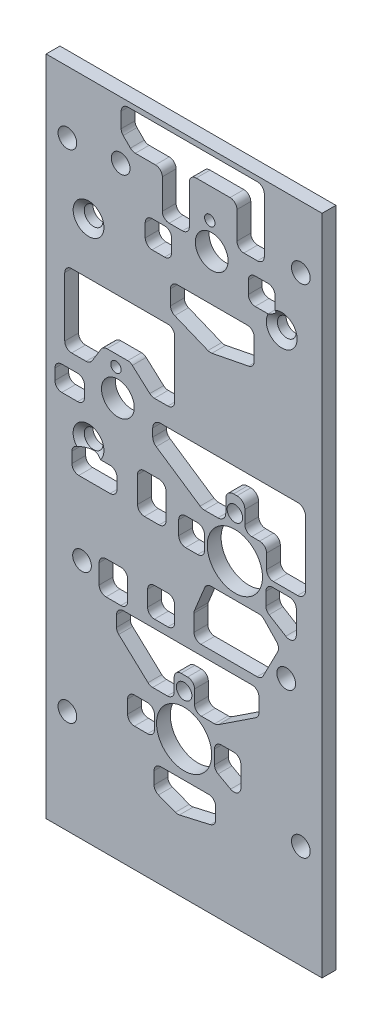
SolidWorks part; units mm, degrees
material "Acrylic (Medium-high impact)"
ref_plane "Front Plane" through (0, 0, 0) normal (0, 0, 1) x (1, 0, 0)
ref_plane "Top Plane" through (0, 0, 0) normal (0, 1, 0) x (1, 0, 0)
ref_plane "Right Plane" through (0, 0, 0) normal (1, 0, 0) x (0, 0, -1)
sketch "Sketch1" plane through (0, 0, 0) normal (0, 0, 1) x (1, 0, 0)
  line L8 (31.75, -152.4) -> (31.75, 0)
  line L9 (31.75, 0) -> (-31.75, 0)
  line L10 (-31.75, 0) -> (-31.75, -152.4)
  line L11 (-31.75, -152.4) -> (31.75, -152.4)
extrude "Boss-Extrude1" add sketch "Sketch1" against normal blind 3.175
hole_wizard "#6 Clearance Hole1" positions "Sketch3" profile "Sketch2" hole size "#6" standard "ANSI Inch" end condition up to next
sketch "Sketch3" plane through (0, 0, 0) normal (0, 0, 1) x (1, 0, 0)
  point P0 (-26.8605, -14.2875)
  point P2 (26.8605, -14.2875)
  point P4 (26.8605, -128.5875)
  point P6 (-26.8605, -128.5875)
sketch "Sketch2" plane through (-26.8605, -14.2875, 0) normal (1, 0, 0) x (0, -1, 0)
  line L0 (0, 0) -> (0, 3.175)
  line L1 (0, 3.175) -> (2.1526, 3.175)
  line L2 (2.1526, 3.175) -> (2.1526, 0)
  line L5 (2.1526, 0) -> (0, 0)
  line L11 (0, -6.35) -> (0, 107.95) construction
  dimension "Thru Hole Dia." = 4.3053
  dimension "Thru Hole Depth" = 3.175
hole_wizard "#6 Clearance Hole2" positions "Sketch5" profile "Sketch4" hole size "#6" standard "ANSI Inch" end condition up to next
sketch "Sketch5" plane through (0, 0, 0) normal (0, 0, 1) x (1, 0, 0)
  point P0 (-23.495, -96.8375)
  point P2 (23.495, -96.8375)
  point P4 (-14.605, -13.208)
sketch "Sketch4" plane through (-23.495, -96.8375, 0) normal (1, 0, 0) x (0, -1, 0)
  line L0 (0, 0) -> (0, 3.175)
  line L1 (0, 3.175) -> (2.1526, 3.175)
  line L2 (2.1526, 3.175) -> (2.1526, 0)
  line L5 (2.1526, 0) -> (0, 0)
  line L11 (0, -6.35) -> (0, 107.95) construction
  dimension "Thru Hole Dia." = 4.3053
  dimension "Thru Hole Depth" = 3.175
hole_wizard "1/2 (0.5) Diameter Hole1" positions "Sketch7" profile "Sketch6" hole size "1/2" standard "ANSI Inch" end condition up to next
sketch "Sketch7" plane through (0, 0, 0) normal (0, 0, 1) x (1, 0, 0)
  point P4 (11.684, -79.375)
  point P6 (0, -120.65)
sketch "Sketch6" plane through (11.684, -79.375, 0) normal (1, 0, 0) x (0, -1, 0)
  line L0 (0, 0) -> (0, 3.175)
  line L1 (0, 3.175) -> (6.35, 3.175)
  line L2 (6.35, 3.175) -> (6.35, 0)
  line L5 (6.35, 0) -> (0, 0)
  line L11 (0, -6.35) -> (0, 107.95) construction
  dimension "Thru Hole Dia." = 12.7
  dimension "Thru Hole Depth" = 3.175
hole_wizard "9/64 (0.14063) Diameter Hole1" positions "Sketch9" profile "Sketch8" hole size "9/64" standard "ANSI Inch" end condition up to next
sketch "Sketch9" plane through (0, 0, 0) normal (0, 0, 1) x (1, 0, 0)
  point P0 (0, -111.125)
  point P2 (11.684, -69.85)
sketch "Sketch8" plane through (0, -111.125, 0) normal (1, 0, 0) x (0, -1, 0)
  line L0 (0, 0) -> (0, 3.175)
  line L1 (0, 3.175) -> (1.786, 3.175)
  line L2 (1.786, 3.175) -> (1.786, 0)
  line L5 (1.786, 0) -> (0, 0)
  line L11 (0, -6.35) -> (0, 107.95) construction
  dimension "Thru Hole Dia." = 3.572
  dimension "Thru Hole Depth" = 3.175
hole_wizard "19/64 (0.29688) Diameter Hole1" positions "Sketch11" profile "Sketch10" hole size "19/64" standard "ANSI Inch" end condition up to next
sketch "Sketch11" plane through (0, 0, 0) normal (0, 0, 1) x (1, 0, 0)
  point P0 (-15.24, -60.325)
  point P2 (6.35, -20.32)
sketch "Sketch10" plane through (-15.24, -60.325, 0) normal (1, 0, 0) x (0, -1, 0)
  line L0 (0, 0) -> (0, 3.175)
  line L1 (0, 3.175) -> (3.7704, 3.175)
  line L2 (3.7704, 3.175) -> (3.7704, 0)
  line L5 (3.7704, 0) -> (0, 0)
  line L11 (0, -6.35) -> (0, 107.95) construction
  dimension "Thru Hole Dia." = 7.5408
  dimension "Thru Hole Depth" = 3.175
hole_wizard "CSK for #6 Flat Head Machine Screw (100)1" positions "Sketch12" profile "Sketch13" countersink size "#6" standard "ANSI Inch" end condition up to next
sketch "Sketch12" plane through (0, 0, 0) normal (0, 0, 1) x (1, 0, 0)
  circle A0 centre (-21.99, -72.39) radius 2.15 construction
  circle A1 centre (-21.99, -27.94) radius 2.15 construction
  circle A2 centre (22.46, -27.94) radius 2.15 construction
  point P0 (-21.99, -72.39)
  point P5 (-21.99, -27.94)
  point P7 (22.46, -27.94)
sketch "Sketch13" plane through (-21.99, -72.39, 0) normal (1, 0, 0) x (0, -1, 0)
  line L0 (0, 0) -> (0, 3.175)
  line L1 (0, 3.175) -> (2.1526, 3.175)
  line L2 (2.1526, 3.175) -> (2.1526, 1.1669)
  line L3 (2.1526, 1.1669) -> (3.5433, 0)
  line L5 (3.5433, 0) -> (0, 0)
  line L6 (-2.1526, 1.1669) -> (-3.5433, 0) construction
  line L11 (0, -6.35) -> (0, 107.95) construction
  dimension "Thru Hole Dia." = 4.3053
  dimension "Thru Hole Depth" = 3.175
  dimension "Near C'Sink Dia." = 7.0866
  dimension "Near C'Sink Angle" = 100
hole_wizard "3/32 (0.09375) Diameter Hole1" positions "Sketch14" profile "Sketch15" hole size "3/32" standard "ANSI Inch" end condition up to next
sketch "Sketch14" plane through (0, 0, 0) normal (0, 0, 1) x (1, 0, 0)
  line L0 (-11.9489, -54.0615) -> (-19.4279, -54.622) construction
  line L1 (9.6411, -14.0565) -> (2.1621, -14.617) construction
  point P0 (-15.6884, -54.3418)
  point P4 (5.9016, -14.3368)
sketch "Sketch15" plane through (-15.6884, -54.3418, 0) normal (1, 0, 0) x (0, -1, 0)
  line L0 (0, 0) -> (0, 3.175)
  line L1 (0, 3.175) -> (1.1906, 3.175)
  line L2 (1.1906, 3.175) -> (1.1906, 0)
  line L5 (1.1906, 0) -> (0, 0)
  line L11 (0, -6.35) -> (0, 107.95) construction
  dimension "Thru Hole Dia." = 2.3812
  dimension "Thru Hole Depth" = 3.175
sketch "Sketch16" plane through (0, 0, 0) normal (0, 0, 1) x (1, 0, 0)
  line L0 (-8.9463, -22.2122) -> (-8.9463, -25.2501)
  line L1 (-12.8969, -1.1704) -> (16.8634, -1.1704)
  line L2 (18.4509, -2.7579) -> (18.4509, -15.3315)
  line L3 (16.8634, -16.919) -> (13.7539, -16.919)
  line L4 (12.1664, -15.3315) -> (12.1664, -9.0413)
  line L5 (10.5789, -7.4538) -> (2.798, -7.4538)
  line L6 (1.2105, -9.0413) -> (1.2105, -17.9777)
  line L7 (-0.377, -19.5652) -> (-3.4256, -19.5652)
  line L8 (-5.0131, -17.9777) -> (-5.0131, -11.1146)
  line L9 (-6.6006, -9.5271) -> (-11.2247, -9.5271)
  line L10 (-12.3472, -9.0621) -> (-14.0195, -7.3899)
  line L11 (-14.4844, -6.2674) -> (-14.4844, -2.7579)
  line L12 (-7.3588, -20.6247) -> (-4.4726, -20.6247)
  line L13 (-2.8851, -22.2122) -> (-2.8851, -25.2501)
  line L14 (-4.4726, -26.8376) -> (-7.3588, -26.8376)
  line L15 (14.7691, -21.7812) -> (14.7691, -24.6709)
  line L16 (16.3566, -26.2584) -> (19.3318, -26.2584)
  line L17 (20.9193, -24.6709) -> (20.9193, -21.7812)
  line L18 (19.3318, -20.1937) -> (16.3566, -20.1937)
  line L19 (-1.5492, -30.8932) -> (14.5429, -30.8932)
  line L20 (16.1304, -32.4807) -> (16.1304, -37.3513)
  line L21 (14.8494, -38.909) -> (6.3904, -40.5735)
  line L22 (5.4811, -40.4844) -> (-2.152, -37.3513)
  line L23 (-3.1367, -35.8827) -> (-3.1367, -32.4807)
  line L24 (-25.8787, -39.8413) -> (-3.7395, -39.8413)
  line L25 (-2.152, -41.4288) -> (-2.152, -54.5712)
  line L26 (-3.7395, -56.1587) -> (-6.8312, -56.1587)
  line L27 (-7.8927, -55.7517) -> (-11.9102, -52.1393)
  line L28 (-12.9716, -51.7323) -> (-17.7428, -51.7323)
  line L29 (-19.0941, -52.4865) -> (-21.1969, -55.8964)
  line L30 (-22.5481, -56.6506) -> (-25.8787, -56.6506)
  line L31 (-27.4662, -55.0631) -> (-27.4662, -41.4288)
  line L32 (-28.1475, -60.0018) -> (-24.5023, -60.0018)
  line L33 (-22.9148, -61.5893) -> (-22.9148, -64.0639)
  line L34 (-24.5023, -65.6514) -> (-28.1475, -65.6514)
  line L35 (-29.735, -64.0639) -> (-29.735, -61.5893)
  line L36 (-5.4046, -60.4477) -> (26.1238, -60.4477)
  line L37 (27.9362, -62.2601) -> (27.9362, -77.1663)
  line L38 (26.1238, -78.9787) -> (20.5606, -78.9787)
  line L40 (13.9861, -70.9353) -> (13.9861, -67.9021)
  line L41 (12.1737, -66.0897) -> (11.3976, -66.0897)
  line L42 (9.5852, -67.9021) -> (9.5852, -70.8813)
  line L43 (7.7728, -72.6937) -> (4.6983, -72.6937)
  line L44 (3.687, -72.3854) -> (-6.4159, -65.5923)
  line L45 (-7.217, -64.0882) -> (-7.217, -62.2601)
  line L46 (-10.7238, -73.3212) -> (-10.7238, -79.2675)
  line L47 (-9.1363, -80.855) -> (-5.7548, -80.855)
  line L48 (-4.1673, -79.2675) -> (-4.1673, -73.3212)
  line L49 (-5.7548, -71.7337) -> (-9.1363, -71.7337)
  line L50 (-24.2328, -74.6188) -> (-17.0395, -74.6188)
  line L51 (-15.452, -76.2063) -> (-15.452, -78.6488)
  line L52 (-17.0395, -80.2363) -> (-24.2328, -80.2363)
  line L53 (-25.8203, -78.6488) -> (-25.8203, -76.2063)
  line L54 (0.3424, -75.984) -> (3.1108, -75.984)
  line L55 (4.6983, -77.5715) -> (4.6983, -80.74)
  line L56 (3.1108, -82.3275) -> (0.3424, -82.3275)
  line L57 (-1.2451, -80.74) -> (-1.2451, -77.5715)
  line L58 (24.2295, -80.2363) -> (20.397, -80.2363)
  line L59 (18.8095, -81.8238) -> (18.8095, -84.7457)
  line L60 (19.5645, -86.0974) -> (23.397, -88.4579)
  line L61 (25.817, -87.1062) -> (25.817, -81.8238)
  line L62 (6.2151, -87.1062) -> (17.232, -87.1062)
  line L66 (16.7933, -99.8291) -> (3.862, -99.8291)
  line L67 (2.2745, -98.2416) -> (2.2745, -94.4383)
  line L68 (2.3929, -93.8366) -> (4.7461, -88.092)
  line L70 (18.2045, -98.9687) -> (21.5565, -92.4623)
  line L71 (21.2917, -90.6372) -> (18.3784, -87.5956)
  line L72 (-17.9633, -93.6958) -> (-14.5591, -93.6958)
  line L73 (-12.9716, -95.2833) -> (-12.9716, -99.7266)
  line L74 (-14.5591, -101.3141) -> (-17.9633, -101.3141)
  line L75 (-19.5508, -99.7266) -> (-19.5508, -95.2833)
  line L76 (-6.8147, -93.4357) -> (-3.7395, -93.4357)
  line L77 (-2.152, -95.0232) -> (-2.152, -98.5745)
  line L78 (-3.7395, -100.162) -> (-6.8147, -100.162)
  line L79 (-8.4022, -98.5745) -> (-8.4022, -95.0232)
  line L80 (-13.9592, -102.0646) -> (15.6445, -102.0646)
  line L81 (17.232, -103.6521) -> (17.232, -106.8148)
  line L82 (16.5194, -108.1395) -> (7.8736, -113.8498)
  line L83 (6.9987, -114.1127) -> (3.9804, -114.1127)
  line L84 (2.3929, -112.5252) -> (2.3929, -109.4802)
  line L85 (0.8054, -107.8927) -> (-0.6914, -107.8927)
  line L86 (-2.2789, -109.4802) -> (-2.2789, -112.4007)
  line L87 (-3.8664, -113.9882) -> (-7.2276, -113.9882)
  line L88 (-8.3063, -113.5654) -> (-15.0379, -107.3311)
  line L89 (-15.5467, -106.1663) -> (-15.5467, -103.6521)
  line L90 (-11.4225, -117.5966) -> (-8.4022, -117.5966)
  line L91 (-6.8147, -119.1841) -> (-6.8147, -122.2054)
  line L92 (-8.4022, -123.7929) -> (-11.4225, -123.7929)
  line L93 (-13.01, -122.2054) -> (-13.01, -119.1841)
  line L94 (13.0588, -123.895) -> (13.0588, -119.1357)
  line L95 (11.4713, -117.5482) -> (8.5862, -117.5482)
  line L96 (6.9987, -119.1357) -> (6.9987, -122.3052)
  line L97 (7.82, -123.6955) -> (10.7052, -125.2854)
  line L98 (-5.3306, -128.8529) -> (5.6668, -128.8529)
  line L99 (7.2543, -130.4404) -> (7.2543, -133.1501)
  line L100 (6.0204, -134.6977) -> (-1.0759, -136.3192)
  line L101 (-2.002, -136.2523) -> (-5.9031, -134.7439)
  line L102 (-6.9181, -133.2633) -> (-6.9181, -130.4404)
  line L103 (18.9731, -77.3912) -> (18.9731, -74.1103)
  line L104 (17.3856, -72.5228) -> (15.5736, -72.5228)
  arc A0 (16.8634, -1.1704) -> (18.4509, -2.7579) centre (16.8634, -2.7579) cw
  arc A1 (18.4509, -15.3315) -> (16.8634, -16.919) centre (16.8634, -15.3315) cw
  arc A2 (13.7539, -16.919) -> (12.1664, -15.3315) centre (13.7539, -15.3315) cw
  arc A3 (12.1664, -9.0413) -> (10.5789, -7.4538) centre (10.5789, -9.0413) ccw
  arc A4 (2.798, -7.4538) -> (1.2105, -9.0413) centre (2.798, -9.0413) ccw
  arc A5 (1.2105, -17.9777) -> (-0.377, -19.5652) centre (-0.377, -17.9777) cw
  arc A6 (-3.4256, -19.5652) -> (-5.0131, -17.9777) centre (-3.4256, -17.9777) cw
  arc A7 (-5.0131, -11.1146) -> (-6.6006, -9.5271) centre (-6.6006, -11.1146) ccw
  arc A8 (-11.2247, -9.5271) -> (-12.3472, -9.0621) centre (-11.2247, -7.9396) cw
  arc A9 (-14.0195, -7.3899) -> (-14.4844, -6.2674) centre (-12.8969, -6.2674) cw
  arc A10 (-12.8969, -1.1704) -> (-14.4844, -2.7579) centre (-12.8969, -2.7579) ccw
  arc A11 (-7.3588, -26.8376) -> (-8.9463, -25.2501) centre (-7.3588, -25.2501) cw
  arc A12 (-2.8851, -25.2501) -> (-4.4726, -26.8376) centre (-4.4726, -25.2501) cw
  arc A13 (-4.4726, -20.6247) -> (-2.8851, -22.2122) centre (-4.4726, -22.2122) cw
  arc A14 (-7.3588, -20.6247) -> (-8.9463, -22.2122) centre (-7.3588, -22.2122) ccw
  arc A15 (20.9193, -21.7812) -> (19.3318, -20.1937) centre (19.3318, -21.7812) ccw
  arc A16 (19.3318, -26.2584) -> (20.9193, -24.6709) centre (19.3318, -24.6709) ccw
  arc A17 (14.7691, -24.6709) -> (16.3566, -26.2584) centre (16.3566, -24.6709) ccw
  arc A18 (14.7691, -21.7812) -> (16.3566, -20.1937) centre (16.3566, -21.7812) cw
  arc A19 (14.5429, -30.8932) -> (16.1304, -32.4807) centre (14.5429, -32.4807) cw
  arc A20 (16.1304, -37.3513) -> (14.8494, -38.909) centre (14.5429, -37.3513) cw
  arc A21 (6.3904, -40.5735) -> (5.4811, -40.4844) centre (6.0839, -39.0158) cw
  arc A22 (-2.152, -37.3513) -> (-3.1367, -35.8827) centre (-1.5492, -35.8827) cw
  arc A23 (-1.5492, -30.8932) -> (-3.1367, -32.4807) centre (-1.5492, -32.4807) ccw
  arc A24 (-25.8787, -56.6506) -> (-27.4662, -55.0631) centre (-25.8787, -55.0631) cw
  arc A25 (-21.1969, -55.8964) -> (-22.5481, -56.6506) centre (-22.5481, -55.0631) cw
  arc A26 (-17.7428, -51.7323) -> (-19.0941, -52.4865) centre (-17.7428, -53.3198) ccw
  arc A27 (-11.9102, -52.1393) -> (-12.9716, -51.7323) centre (-12.9716, -53.3198) ccw
  arc A28 (-6.8312, -56.1587) -> (-7.8927, -55.7517) centre (-6.8312, -54.5712) cw
  arc A29 (-2.152, -54.5712) -> (-3.7395, -56.1587) centre (-3.7395, -54.5712) cw
  arc A30 (-3.7395, -39.8413) -> (-2.152, -41.4288) centre (-3.7395, -41.4288) cw
  arc A31 (-25.8787, -39.8413) -> (-27.4662, -41.4288) centre (-25.8787, -41.4288) ccw
  arc A32 (-28.1475, -65.6514) -> (-29.735, -64.0639) centre (-28.1475, -64.0639) cw
  arc A33 (-22.9148, -64.0639) -> (-24.5023, -65.6514) centre (-24.5023, -64.0639) cw
  arc A34 (-24.5023, -60.0018) -> (-22.9148, -61.5893) centre (-24.5023, -61.5893) cw
  arc A35 (-28.1475, -60.0018) -> (-29.735, -61.5893) centre (-28.1475, -61.5893) ccw
  arc A36 (26.1238, -60.4477) -> (27.9362, -62.2601) centre (26.1238, -62.2601) cw
  arc A37 (27.9362, -77.1663) -> (26.1238, -78.9787) centre (26.1238, -77.1663) cw
  arc A40 (13.9861, -67.9021) -> (12.1737, -66.0897) centre (12.1737, -67.9021) ccw
  arc A41 (11.3976, -66.0897) -> (9.5852, -67.9021) centre (11.3976, -67.9021) ccw
  arc A42 (9.5852, -70.8813) -> (7.7728, -72.6937) centre (7.7728, -70.8813) cw
  arc A43 (4.6983, -72.6937) -> (3.687, -72.3854) centre (4.6983, -70.8813) cw
  arc A44 (-6.4159, -65.5923) -> (-7.217, -64.0882) centre (-5.4046, -64.0882) cw
  arc A45 (-5.4046, -60.4477) -> (-7.217, -62.2601) centre (-5.4046, -62.2601) ccw
  arc A46 (-4.1673, -73.3212) -> (-5.7548, -71.7337) centre (-5.7548, -73.3212) ccw
  arc A47 (-5.7548, -80.855) -> (-4.1673, -79.2675) centre (-5.7548, -79.2675) ccw
  arc A48 (-10.7238, -79.2675) -> (-9.1363, -80.855) centre (-9.1363, -79.2675) ccw
  arc A49 (-10.7238, -73.3212) -> (-9.1363, -71.7337) centre (-9.1363, -73.3212) cw
  arc A50 (-24.2328, -80.2363) -> (-25.8203, -78.6488) centre (-24.2328, -78.6488) cw
  arc A51 (-15.452, -78.6488) -> (-17.0395, -80.2363) centre (-17.0395, -78.6488) cw
  arc A52 (-17.0395, -74.6188) -> (-15.452, -76.2063) centre (-17.0395, -76.2063) cw
  arc A53 (-24.2328, -74.6188) -> (-25.8203, -76.2063) centre (-24.2328, -76.2063) ccw
  arc A54 (3.1108, -75.984) -> (4.6983, -77.5715) centre (3.1108, -77.5715) cw
  arc A55 (4.6983, -80.74) -> (3.1108, -82.3275) centre (3.1108, -80.74) cw
  arc A56 (0.3424, -82.3275) -> (-1.2451, -80.74) centre (0.3424, -80.74) cw
  arc A57 (0.3424, -75.984) -> (-1.2451, -77.5715) centre (0.3424, -77.5715) ccw
  arc A58 (23.397, -88.4579) -> (25.817, -87.1062) centre (24.2295, -87.1062) ccw
  arc A59 (18.8095, -84.7457) -> (19.5645, -86.0974) centre (20.397, -84.7457) ccw
  arc A60 (20.397, -80.2363) -> (18.8095, -81.8238) centre (20.397, -81.8238) ccw
  arc A61 (24.2295, -80.2363) -> (25.817, -81.8238) centre (24.2295, -81.8238) cw
  arc A65 (3.862, -99.8291) -> (2.2745, -98.2416) centre (3.862, -98.2416) cw
  arc A66 (2.2745, -94.4383) -> (2.3929, -93.8366) centre (3.862, -94.4383) cw
  arc A67 (6.2151, -87.1062) -> (4.7461, -88.092) centre (6.2151, -88.6937) ccw
  arc A68 (16.7933, -99.8291) -> (18.2045, -98.9687) centre (16.7933, -98.2416) ccw
  arc A69 (21.5565, -92.4623) -> (21.2917, -90.6372) centre (20.1453, -91.7353) ccw
  arc A70 (17.232, -87.1062) -> (18.3784, -87.5956) centre (17.232, -88.6937) cw
  arc A71 (-17.9633, -101.3141) -> (-19.5508, -99.7266) centre (-17.9633, -99.7266) cw
  arc A72 (-12.9716, -99.7266) -> (-14.5591, -101.3141) centre (-14.5591, -99.7266) cw
  arc A73 (-14.5591, -93.6958) -> (-12.9716, -95.2833) centre (-14.5591, -95.2833) cw
  arc A74 (-17.9633, -93.6958) -> (-19.5508, -95.2833) centre (-17.9633, -95.2833) ccw
  arc A75 (-6.8147, -100.162) -> (-8.4022, -98.5745) centre (-6.8147, -98.5745) cw
  arc A76 (-2.152, -98.5745) -> (-3.7395, -100.162) centre (-3.7395, -98.5745) cw
  arc A77 (-3.7395, -93.4357) -> (-2.152, -95.0232) centre (-3.7395, -95.0232) cw
  arc A78 (-6.8147, -93.4357) -> (-8.4022, -95.0232) centre (-6.8147, -95.0232) ccw
  arc A79 (-7.2276, -113.9882) -> (-8.3063, -113.5654) centre (-7.2276, -112.4007) cw
  arc A80 (-15.0379, -107.3311) -> (-15.5467, -106.1663) centre (-13.9592, -106.1663) cw
  arc A81 (-13.9592, -102.0646) -> (-15.5467, -103.6521) centre (-13.9592, -103.6521) ccw
  arc A82 (15.6445, -102.0646) -> (17.232, -103.6521) centre (15.6445, -103.6521) cw
  arc A83 (17.232, -106.8148) -> (16.5194, -108.1395) centre (15.6445, -106.8148) cw
  arc A84 (7.8736, -113.8498) -> (6.9987, -114.1127) centre (6.9987, -112.5252) cw
  arc A85 (3.9804, -114.1127) -> (2.3929, -112.5252) centre (3.9804, -112.5252) cw
  arc A86 (-2.2789, -112.4007) -> (-3.8664, -113.9882) centre (-3.8664, -112.4007) cw
  arc A87 (2.3929, -109.4802) -> (0.8054, -107.8927) centre (0.8054, -109.4802) ccw
  arc A88 (-0.6914, -107.8927) -> (-2.2789, -109.4802) centre (-0.6914, -109.4802) ccw
  arc A89 (-8.4022, -117.5966) -> (-6.8147, -119.1841) centre (-8.4022, -119.1841) cw
  arc A90 (-6.8147, -122.2054) -> (-8.4022, -123.7929) centre (-8.4022, -122.2054) cw
  arc A91 (-11.4225, -123.7929) -> (-13.01, -122.2054) centre (-11.4225, -122.2054) cw
  arc A92 (-11.4225, -117.5966) -> (-13.01, -119.1841) centre (-11.4225, -119.1841) ccw
  arc A93 (6.9987, -122.3052) -> (7.82, -123.6955) centre (8.5862, -122.3052) ccw
  arc A94 (8.5862, -117.5482) -> (6.9987, -119.1357) centre (8.5862, -119.1357) ccw
  arc A95 (13.0588, -119.1357) -> (11.4713, -117.5482) centre (11.4713, -119.1357) ccw
  arc A96 (13.0588, -123.895) -> (10.7052, -125.2854) centre (11.4713, -123.895) cw
  arc A97 (5.6668, -128.8529) -> (7.2543, -130.4404) centre (5.6668, -130.4404) cw
  arc A98 (7.2543, -133.1501) -> (6.0204, -134.6977) centre (5.6668, -133.1501) cw
  arc A99 (-1.0759, -136.3192) -> (-2.002, -136.2523) centre (-1.4295, -134.7716) cw
  arc A100 (-5.9031, -134.7439) -> (-6.9181, -133.2633) centre (-5.3306, -133.2633) cw
  arc A101 (-5.3306, -128.8529) -> (-6.9181, -130.4404) centre (-5.3306, -130.4404) ccw
  arc A102 (20.5606, -78.9787) -> (18.9731, -77.3912) centre (20.5606, -77.3912) cw
  arc A103 (13.9861, -70.9353) -> (15.5736, -72.5228) centre (15.5736, -70.9353) ccw
  arc A104 (18.9731, -74.1103) -> (17.3856, -72.5228) centre (17.3856, -74.1103) ccw
  dimension "D1" = 1.5875
  dimension "D2" = 1.5875
  dimension "D3" = 1.5875
  dimension "D4" = 1.5875
  dimension "D5" = 1.5875
  dimension "D6" = 1.5875
  dimension "D7" = 1.8124
  dimension "D8" = 1.5875
  dimension "D9" = 1.5875
  dimension "D10" = 1.5875
  dimension "D11" = 1.5875
  dimension "D12" = 1.5875
  dimension "D13" = 1.5875
  dimension "D14" = 1.5875
  dimension "D15" = 1.5875
  dimension "D16" = 1.5875
  dimension "D17" = 1.5875
  dimension "D18" = 1.5875
  dimension "D19" = 1.5875
extrude "Cut-Extrude1" cut sketch "Sketch16" against normal through all
